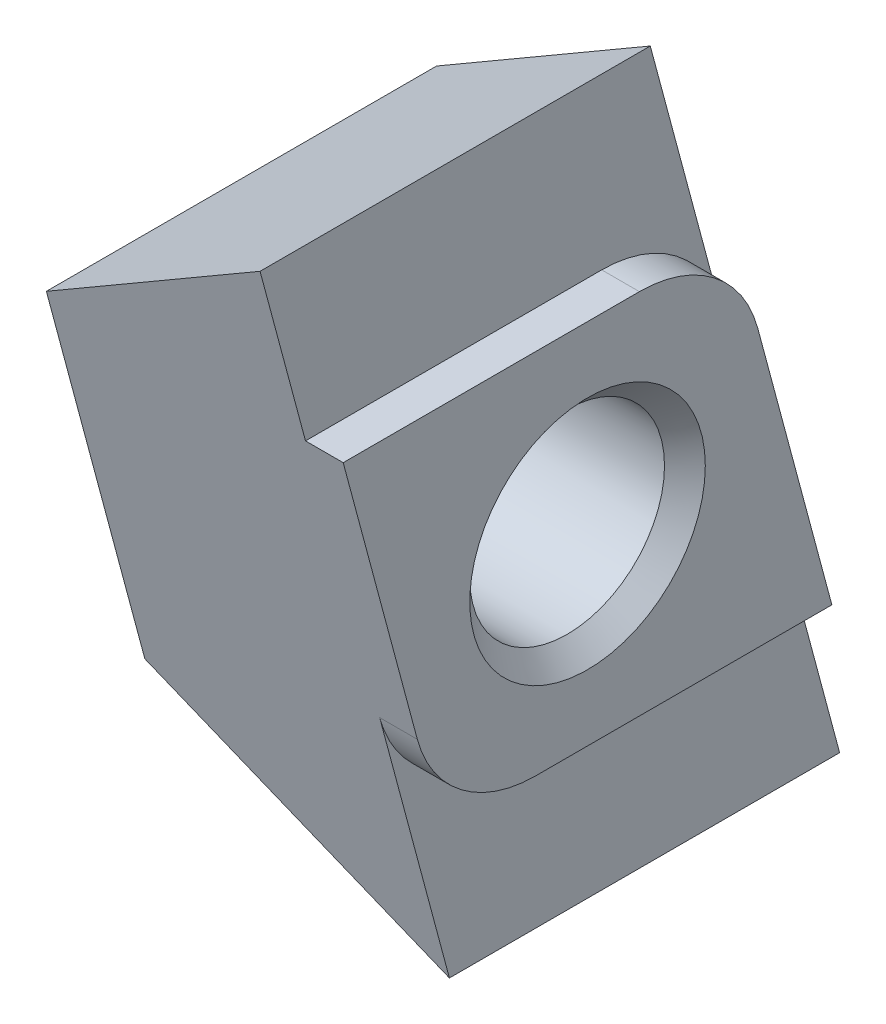
SolidWorks part; units mm, degrees
ref_plane "Piano frontale" through (0, 0, 0) normal (0, 0, 1) x (1, 0, 0)
ref_plane "Piano superiore" through (0, 0, 0) normal (0, 1, 0) x (1, 0, 0)
ref_plane "Piano destro" through (0, 0, 0) normal (1, 0, 0) x (0, 0, -1)
sketch "Sketch1" plane through (0, 0, 0) normal (1, 0, 0) x (0, 0, -1)
  line L0 (1.1011, 3.9) -> (-5.1861, 3.9)
  line L1 (-5.1861, 3.9) -> (-3.6125, -1.9729)
  line L2 (-1.1011, -3.9) -> (5.1861, -3.9)
  line L3 (5.1861, -3.9) -> (3.6125, 1.9729)
  arc A0 (-3.6125, -1.9729) -> (-1.1011, -3.9) centre (-1.1011, -1.3) ccw
  arc A1 (3.6125, 1.9729) -> (1.1011, 3.9) centre (1.1011, 1.3) ccw
extrude "Extrude1" add sketch "Sketch1" against normal blind 0.8
sketch "Sketch2" plane through (-0.8, 0, 0) normal (-1, 0, 0) x (0, 0, 1)
  line L0 (2.1315, -7.5) -> (-6.1507, -7.5)
  line L1 (-2.1315, 7.5) -> (6.1507, 7.5)
  spline S0 degree 3 poles (-2.1315, 7.5) (-3.4712, 2.5) (-4.811, -2.5) (-6.1507, -7.5) knots 0 0 0 0 1 1 1 1
  spline S1 degree 3 poles (2.1315, -7.5) (3.4712, -2.5) (4.811, 2.5) (6.1507, 7.5) knots 0 0 0 0 1 1 1 1
extrude "Extrude2" add sketch "Sketch2" along normal blind 5.5
draft "Draft1" type of draft neutral plane draft angle 33.207 faces to draft 1 face at (-3.55, 7.5, 2.0096) neutral plane through (-0.8, 0, 4.1411) neutral plane normal (1, 0, 0) reverse direction yes parameters "D1"=33.207
draft "Draft2" type of draft neutral plane draft angle 33.207 faces to draft 1 face at (-3.55, -7.5, -2.0096) neutral plane through (-0.8, 0, 4.1411) neutral plane normal (1, 0, 0) reverse direction yes parameters "D1"=33.207
hole_wizard "HoleWzd1" positions "Sketch4" profile "Sketch3" hole size "M3.5" standard "Ansi Metric"
sketch "Sketch4" plane through (-6.3, 0, 0) normal (-1, 0, 0) x (0, 0, 1)
  point P0 (0, 0)
sketch "Sketch3" plane through (-6.3, 0, 0) normal (0, 1, 0) x (0, 0, 1)
  line L0 (0, 0) -> (0, 6.3)
  line L1 (0, 6.3) -> (2.067, 6.3)
  line L2 (2.067, 6.3) -> (2.067, 0)
  line L5 (2.067, 0) -> (0, 0)
  line L11 (0, -6.35) -> (0, 107.95) construction
  dimension "Thru Hole Dia." = 4.134
  dimension "Thru Hole Depth" = 6.3
chamfer "Chamfer1" distance 0.433 angle 45 2 edges at (0, 0, -2.067) (-6.3, 0, 2.067)
